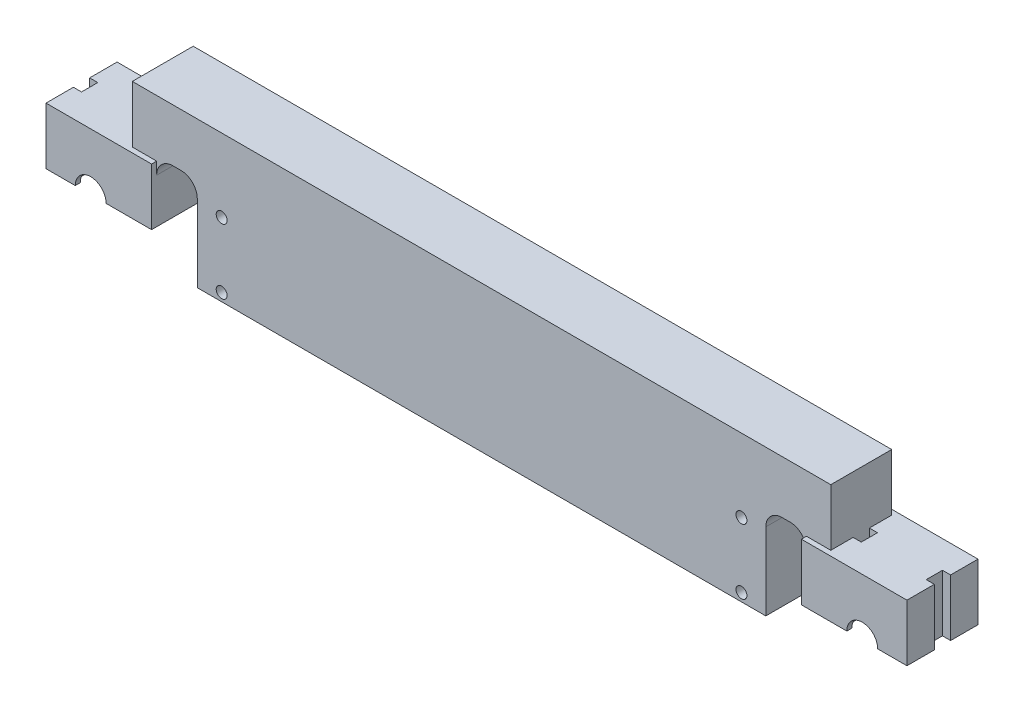
SolidWorks part; units mm, degrees
ref_plane "Front Plane" through (0, 0, 0) normal (0, 0, 1) x (1, 0, 0)
ref_plane "Top Plane" through (0, 0, 0) normal (0, 1, 0) x (1, 0, 0)
ref_plane "Right Plane" through (0, 0, 0) normal (1, 0, 0) x (0, 0, -1)
sketch "Sketch1" plane through (0, 0, 0) normal (0, 0, 1) x (1, 0, 0)
  line L0 (-109.22, 0) -> (-134.62, 0)
  line L1 (-109.22, 17.78) -> (109.22, 17.78)
  line L2 (-109.22, 17.78) -> (-109.22, 0)
  line L3 (-109.22, -17.78) -> (-101.6, -17.78)
  line L4 (109.22, 17.78) -> (109.22, 0)
  line L5 (-109.22, 17.78) -> (109.22, -17.78) construction
  line L6 (-109.22, -17.78) -> (109.22, 17.78) construction
  line L7 (-134.62, 0) -> (-134.62, -17.78)
  line L8 (-127, -17.78) -> (-134.62, -17.78)
  line L9 (-114.3, -17.78) -> (-109.22, -17.78)
  line L10 (0, 0) -> (0, 17.78) construction
  line L11 (114.3, -17.78) -> (109.22, -17.78)
  line L12 (127, -17.78) -> (134.62, -17.78)
  line L13 (134.62, 0) -> (134.62, -17.78)
  line L14 (109.22, 0) -> (134.62, 0)
  line L15 (0, 0) -> (-134.62, 0) construction
  line L16 (-101.6, -17.78) -> (-101.6, -3.81)
  line L17 (-88.9, -17.78) -> (-88.9, -27.94)
  line L18 (-96.52, 1.27) -> (-93.98, 1.27)
  line L19 (-88.9, -3.81) -> (-88.9, -17.78)
  line L20 (-88.9, -27.94) -> (88.9, -27.94)
  line L21 (0, 0) -> (0, -27.94) construction
  line L22 (101.6, -17.78) -> (101.6, -3.81)
  line L23 (96.52, 1.27) -> (93.98, 1.27)
  line L24 (88.9, -3.81) -> (88.9, -17.78)
  line L26 (101.6, -17.78) -> (109.22, -17.78)
  line L27 (88.9, -27.94) -> (88.9, -17.78)
  arc A0 (-127, -17.78) -> (-114.3, -17.78) centre (-120.65, -17.78) cw
  arc A1 (127, -17.78) -> (114.3, -17.78) centre (120.65, -17.78) ccw
  arc A7 (101.6, -3.81) -> (96.52, 1.27) centre (96.52, -3.81) ccw
  arc A8 (88.9, -3.81) -> (93.98, 1.27) centre (93.98, -3.81) cw
  arc A9 (-88.9, -3.81) -> (-93.98, 1.27) centre (-93.98, -3.81) ccw
  arc A10 (-101.6, -3.81) -> (-96.52, 1.27) centre (-96.52, -3.81) cw
  circle A11 centre (-81.28, -25.4) radius 1.7
  circle A12 centre (-81.28, -5.08) radius 1.7
  circle A13 centre (81.28, -25.4) radius 1.7
  circle A14 centre (81.28, -5.08) radius 1.7
  point P0 (0, 0)
  point P33 (101.6, 1.27)
  point P38 (88.9, 1.27)
  point P45 (-88.9, 1.27)
  point P48 (-101.6, 1.27)
  dimension "D5" = 12.7
  dimension "D6" = 10.16
  dimension "D11" = 5.08
  dimension "D8" = 3.4
  dimension "D1" = 241.3
  dimension "D2" = 35.56
  dimension "D3" = 25.4
  dimension "D4" = 17.78
  dimension "D7" = 177.8
  dimension "D9" = 19.05
  dimension "D10" = 12.7
  dimension "D12" = 20.32
  dimension "D13" = 218.44
  dimension "D14" = 22.86
  dimension "D15" = 7.62
extrude "Boss-Extrude1" add sketch "Sketch1" along normal blind 9.525 and the other way blind 9.525
sketch "Sketch2" plane through (0, 0, 0) normal (0, 1, 0) x (1, 0, 0)
  line L0 (-121.92, 9.525) -> (-121.92, -9.525) construction
  line L1 (-111.76, 2.54) -> (-109.22, 2.54)
  line L2 (-111.76, 2.54) -> (-111.76, -2.54)
  line L3 (-111.76, -2.54) -> (-109.22, -2.54)
  line L4 (-109.22, 2.54) -> (-109.22, -2.54)
  line L5 (-111.76, 2.54) -> (-109.22, -2.54) construction
  line L6 (-111.76, -2.54) -> (-109.22, 2.54) construction
  line L7 (-109.22, 9.525) -> (-134.62, 9.525) construction
  line L8 (-109.22, -9.525) -> (-134.62, -9.525) construction
  line L9 (-132.08, -2.54) -> (-134.62, -2.54)
  line L10 (-134.62, 2.54) -> (-134.62, -2.54)
  line L11 (-132.08, 2.54) -> (-134.62, 2.54)
  line L12 (-132.08, 2.54) -> (-132.08, -2.54)
  line L13 (0, 0) -> (0, -9.525) construction
  line L14 (109.22, -9.525) -> (-109.22, -9.525) construction
  line L15 (132.08, 2.54) -> (132.08, -2.54)
  line L16 (132.08, 2.54) -> (134.62, 2.54)
  line L17 (134.62, 2.54) -> (134.62, -2.54)
  line L18 (132.08, -2.54) -> (134.62, -2.54)
  line L19 (111.76, -2.54) -> (109.22, -2.54)
  line L20 (109.22, 2.54) -> (109.22, -2.54)
  line L21 (111.76, 2.54) -> (109.22, 2.54)
  line L22 (111.76, 2.54) -> (111.76, -2.54)
  line L23 (-121.92, 0) -> (-110.49, 0) construction
  point P0 (-110.49, 0)
  dimension "D1" = 2.54
  dimension "D2" = 5.08
  dimension "D3" = 11.43
extrude "Cut-Extrude1" cut sketch "Sketch2" against normal blind 27.686
sketch "Sketch3" plane through (0, 0, 9.525) normal (0, 0, 1) x (1, 0, 0)
  line L2 (0, 0) -> (0, 17.78) construction
  line L15 (109.22, 17.78) -> (-109.22, 17.78) construction
  line L30 (-134.62, 0) -> (-101.6, 0)
  line L31 (-101.6, 0) -> (-101.6, -17.78)
  line L32 (-101.6, -17.78) -> (-115.824, -17.78)
  line L33 (-134.62, 0) -> (-134.62, -17.78)
  line L34 (-134.62, -17.78) -> (-125.476, -17.78)
  line L35 (-120.65, -11.43) -> (-120.65, -17.78) construction
  line L36 (120.65, -11.43) -> (120.65, -17.78) construction
  line L37 (134.62, -17.78) -> (125.476, -17.78)
  line L38 (134.62, 0) -> (134.62, -17.78)
  line L39 (101.6, -17.78) -> (115.824, -17.78)
  line L40 (101.6, 0) -> (101.6, -17.78)
  line L41 (134.62, 0) -> (101.6, 0)
  arc A4 (-125.476, -17.78) -> (-115.824, -17.78) centre (-120.65, -17.78) cw
  arc A5 (-114.3, -17.78) -> (-127, -17.78) centre (-120.65, -17.78) ccw construction
  arc A6 (125.476, -17.78) -> (115.824, -17.78) centre (120.65, -17.78) ccw
  dimension "D2" = 9.652
extrude "Boss-Extrude2" add sketch "Sketch3" along normal blind 1.5875
mirror "Mirror1" about plane through (0, 0, 0) normal (0, 0, 1) of "Boss-Extrude2"
